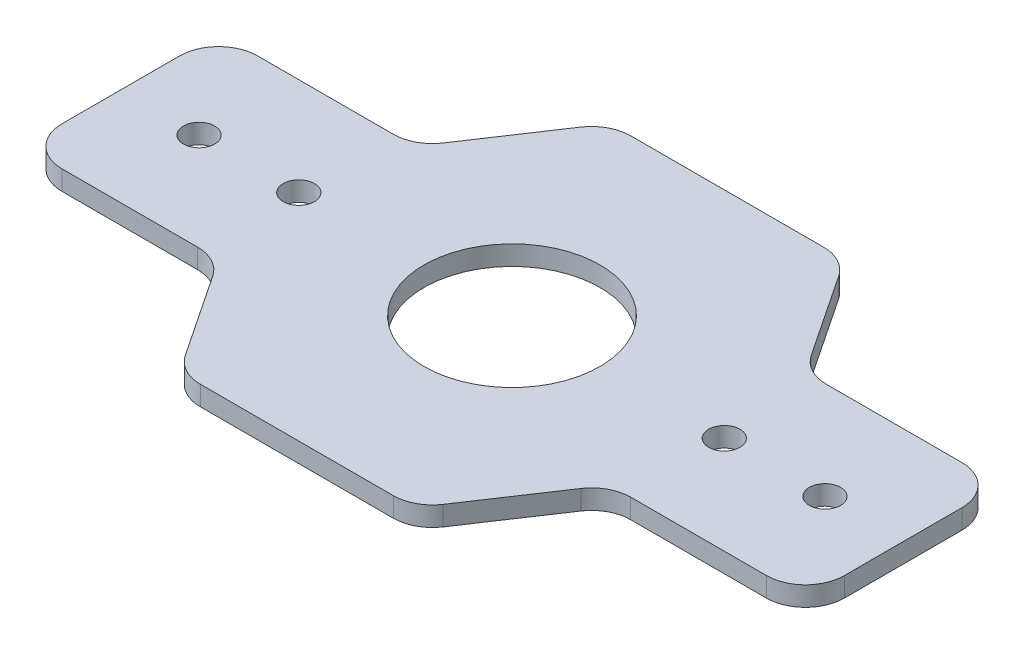
SolidWorks part; units mm, degrees
ref_plane "Front Plane" through (0, 0, 0) normal (0, 0, 1) x (1, 0, 0)
ref_plane "Top Plane" through (0, 0, 0) normal (0, 1, 0) x (1, 0, 0)
ref_plane "Right Plane" through (0, 0, 0) normal (1, 0, 0) x (0, 0, -1)
sketch "Sketch1" plane through (0, 0, 0) normal (0, 1, 0) x (1, 0, 0)
  line L0 (16.2686, 0) -> (85.3314, 0) construction
  line L1 (50.8, 0) -> (50.8, 3.1391) construction
  line L2 (19.05, 15.875) -> (31.75, 34.925)
  line L3 (-12.7, 15.875) -> (19.05, 15.875)
  line L4 (-12.7, 15.875) -> (-12.7, -15.875)
  line L5 (-12.7, -15.875) -> (19.05, -15.875)
  line L6 (114.3, 15.875) -> (114.3, -15.875)
  line L7 (-12.7, 15.875) -> (114.3, -15.875) construction
  line L8 (-12.7, -15.875) -> (114.3, 15.875) construction
  line L9 (31.75, 34.925) -> (69.85, 34.925)
  line L10 (69.85, 34.925) -> (82.55, 15.875)
  line L11 (50.8, 34.925) -> (50.8, 29.0511) construction
  line L12 (69.85, -34.925) -> (82.55, -15.875)
  line L13 (31.75, -34.925) -> (69.85, -34.925)
  line L14 (19.05, -15.875) -> (31.75, -34.925)
  line L15 (82.55, -15.875) -> (114.3, -15.875)
  line L16 (82.55, 15.875) -> (114.3, 15.875)
  circle A0 centre (0, 0) radius 2.54
  circle A1 centre (101.6, 0) radius 2.54
  circle A2 centre (16.2686, 0) radius 2.54 construction
  circle A3 centre (85.3314, 0) radius 2.54 construction
  dimension "D1" = 5.08
  dimension "D3" = 127
  dimension "D4" = 31.75
  dimension "D5" = 69.0628
  dimension "D2" = 101.6
  dimension "D6" = 19.05
  dimension "D7" = 31.75
  dimension "D8" = 38.1
extrude "Boss-Extrude1" add sketch "Sketch1" along normal blind 3.175
fillet "Fillet1" radius 6.35 12 edges at (19.05, 1.5875, -15.875) (31.75, 1.5875, -34.925) (69.85, 1.5875, -34.925) (82.55, 1.5875, -15.875) (114.3, 1.5875, -15.875) (114.3, 1.5875, 15.875) (82.55, 1.5875, 15.875) (69.85, 1.5875, 34.925) (31.75, 1.5875, 34.925) (19.05, 1.5875, 15.875) (-12.7, 1.5875, -15.875) (-12.7, 1.5875, 15.875)
sketch "Sketch2" plane through (0, 3.175, 0) normal (0, 1, 0) x (1, 0, 0)
  circle A0 centre (50.8, 0) radius 14.2875
  circle A1 centre (0, 0) radius 2.54 construction
  dimension "D1" = 50.8
  dimension "D2" = 28.575
extrude "Cut-Extrude1" cut sketch "Sketch2" against normal blind 3.175
sketch "Sketch3" plane through (0, 3.175, 0) normal (0, 1, 0) x (1, 0, 0)
  circle A2 centre (85.2557, 0) radius 2.54
  circle A3 centre (16.1929, 0) radius 2.54
  circle A4 centre (101.6, 0) radius 2.54 construction
  dimension "D1" = 69.0628
  dimension "D2" = 5.08
  dimension "D3" = 5.08
  dimension "D4" = 16.3443
extrude "Cut-Extrude2" cut sketch "Sketch3" against normal through all
